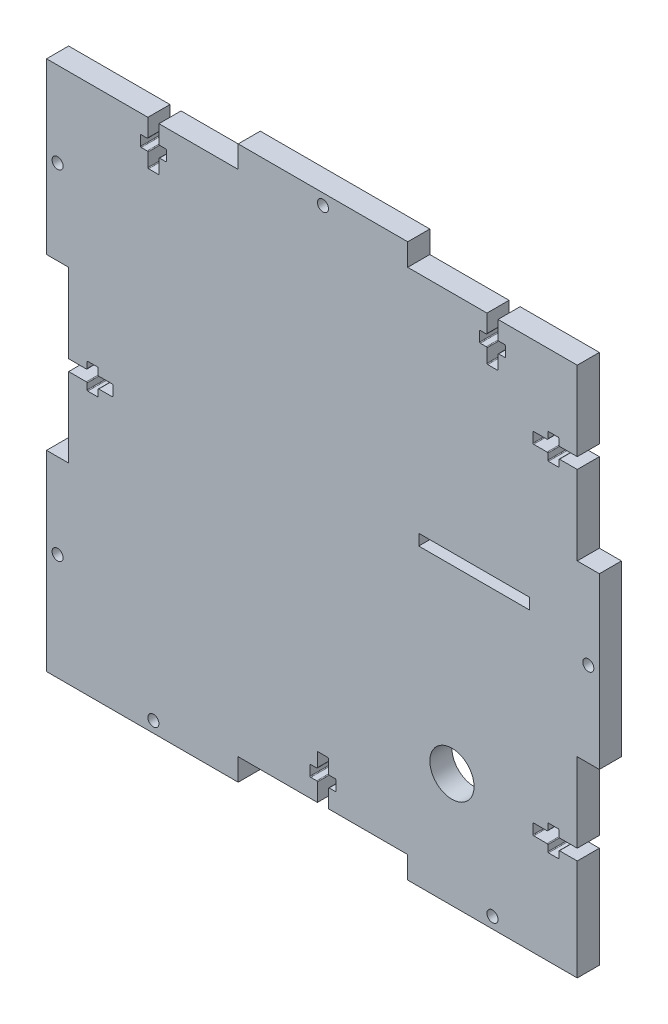
SolidWorks part; units mm, degrees
ref_plane "Front Plane" through (0, 0, 0) normal (0, 0, 1) x (1, 0, 0)
ref_plane "Top Plane" through (0, 0, 0) normal (0, 1, 0) x (1, 0, 0)
ref_plane "Right Plane" through (0, 0, 0) normal (1, 0, 0) x (0, 0, -1)
sketch "Sketch1" plane through (0, 0, 0) normal (0, 0, 1) x (1, 0, 0)
  line L0 (-69, 69) -> (-23, 69)
  line L5 (-75, -75) -> (75, -75) construction
  line L6 (-75, -75) -> (-75, 75) construction
  line L7 (-75, 75) -> (75, 75) construction
  line L8 (75, -75) -> (75, 75) construction
  line L9 (75, 23) -> (69, 23)
  line L10 (69, -23) -> (75, -23)
  line L11 (-69, -69) -> (69, -69) construction
  line L12 (-69, -69) -> (-69, 69) construction
  line L13 (-69, 69) -> (69, 69) construction
  line L14 (69, -69) -> (69, 69) construction
  line L15 (-69, -69) -> (69, 69) construction
  line L16 (69, -69) -> (69, -23)
  line L17 (-23, 69) -> (-23, 75)
  line L18 (-23, 75) -> (23, 75)
  line L19 (23, 75) -> (23, 69)
  line L20 (23, 69) -> (69, 69)
  line L21 (75, -23) -> (75, 23)
  line L22 (69, 23) -> (69, 69)
  line L23 (-75, 23) -> (-69, 23)
  line L24 (-69, 69) -> (-75, 69)
  line L25 (-75, 69) -> (-75, 23)
  line L26 (69, -69) -> (69, -75)
  line L27 (69, -75) -> (23, -75)
  line L28 (23, -75) -> (23, -69)
  line L29 (23, -69) -> (-23, -69)
  line L30 (-23, -69) -> (-23, -75)
  line L31 (-23, -75) -> (-69, -75)
  line L32 (-69, -75) -> (-69, -69) construction
  line L33 (-69, 23) -> (-69, -23)
  line L34 (-69, -23) -> (-75, -23)
  line L35 (-75, -23) -> (-75, -69)
  line L36 (-75, -69) -> (-69, -69) construction
  line L37 (-46, 69) -> (-46, -75) construction
  line L38 (-69, 69) -> (69, -69) construction
  line L39 (-75, -75) -> (-69, -75)
  line L40 (-75, -75) -> (-75, -69)
  point P0 (0, 0)
  point P6 (-7, -7)
  point P26 (0, -75)
  point P27 (-75, 0)
  dimension "D1" = 150
  dimension "D2" = 150
  dimension "D5" = 46
  dimension "D3" = 6
  dimension "D6" = 6
  dimension "D7" = 6
extrude "Box Side" add sketch "Sketch1" along normal blind 6
sketch "Sketch2" plane through (0, 0, 6) normal (0, 0, 1) x (1, 0, 0)
  line L0 (23, 72) -> (-23, 72) construction
  line L1 (23, 75) -> (23, 69) construction
  line L2 (-23, 69) -> (-23, 75) construction
  line L3 (-46, 69) -> (-46, -75) construction
  line L5 (0, 75) -> (0, 69) construction
  line L6 (-23, 75) -> (23, 75) construction
  line L7 (-69, 69) -> (69, 69) construction
  line L16 (-46, 69) -> (-46, -75) construction
  line L21 (0, -69) -> (0, 69) construction
  line L35 (-69, 69) -> (-23, 69) construction
  line L36 (-44.5, 69) -> (-44.5, 64.2)
  line L37 (-44.3, 64) -> (-42.7, 64)
  line L38 (-42.5, 63.8) -> (-42.5, 61.2)
  line L39 (-42.7, 61) -> (-44.3, 61)
  line L40 (-44.5, 60.8) -> (-44.5, 57.2)
  line L46 (-44.7, 57) -> (-47.3, 57)
  line L48 (-44.5, 69) -> (-47.5, 69)
  line L51 (-47.5, 60.8) -> (-47.5, 57.2)
  line L52 (-49.3, 61) -> (-47.7, 61)
  line L53 (-49.5, 63.8) -> (-49.5, 61.2)
  line L54 (-47.7, 64) -> (-49.3, 64)
  line L55 (-47.5, 69) -> (-47.5, 64.2)
  line L56 (47.5, 69) -> (47.5, 64.2)
  line L57 (47.7, 64) -> (49.3, 64)
  line L58 (49.5, 63.8) -> (49.5, 61.2)
  line L59 (49.3, 61) -> (47.7, 61)
  line L60 (47.5, 60.8) -> (47.5, 57.2)
  line L61 (44.5, 69) -> (47.5, 69)
  line L62 (44.7, 57) -> (47.3, 57)
  line L63 (44.5, 60.8) -> (44.5, 57.2)
  line L64 (42.7, 61) -> (44.3, 61)
  line L65 (42.5, 63.8) -> (42.5, 61.2)
  line L66 (44.3, 64) -> (42.7, 64)
  line L67 (44.5, 69) -> (44.5, 64.2)
  line L68 (-69, -69) -> (69, 69) construction
  line L69 (-69, -69) -> (69, 69) construction
  line L70 (75, 0) -> (69, 0) construction
  line L71 (72, 23) -> (72, -23) construction
  line L72 (69, 44.5) -> (64.2, 44.5)
  line L73 (64, 44.3) -> (64, 42.7)
  line L74 (63.8, 42.5) -> (61.2, 42.5)
  line L75 (61, 42.7) -> (61, 44.3)
  line L76 (60.8, 44.5) -> (57.2, 44.5)
  line L77 (57, 44.7) -> (57, 47.3)
  line L78 (69, 44.5) -> (69, 47.5)
  line L79 (60.8, 47.5) -> (57.2, 47.5)
  line L80 (61, 49.3) -> (61, 47.7)
  line L81 (63.8, 49.5) -> (61.2, 49.5)
  line L82 (64, 47.7) -> (64, 49.3)
  line L83 (69, 47.5) -> (64.2, 47.5)
  line L84 (69, -47.5) -> (64.2, -47.5)
  line L85 (64, -47.7) -> (64, -49.3)
  line L86 (63.8, -49.5) -> (61.2, -49.5)
  line L87 (61, -49.3) -> (61, -47.7)
  line L88 (60.8, -47.5) -> (57.2, -47.5)
  line L89 (69, -44.5) -> (69, -47.5)
  line L90 (57, -44.7) -> (57, -47.3)
  line L91 (60.8, -44.5) -> (57.2, -44.5)
  line L92 (61, -42.7) -> (61, -44.3)
  line L93 (63.8, -42.5) -> (61.2, -42.5)
  line L94 (64, -44.3) -> (64, -42.7)
  line L95 (69, -44.5) -> (64.2, -44.5)
  line L120 (-69, 69) -> (69, -69) construction
  line L121 (-69, 69) -> (69, -69) construction
  line L122 (-1.5, -69) -> (1.5, -69)
  line L123 (-23, -69) -> (23, -69) construction
  line L124 (1.5, -69) -> (1.5, -64.2)
  line L125 (1.7, -64) -> (3.3, -64)
  line L126 (3.5, -63.8) -> (3.5, -61.2)
  line L127 (3.3, -61) -> (1.7, -61)
  line L128 (1.5, -60.8) -> (1.5, -57.2)
  line L129 (1.3, -57) -> (-1.3, -57)
  line L130 (-1.5, -60.8) -> (-1.5, -57.2)
  line L131 (-3.3, -61) -> (-1.7, -61)
  line L132 (-3.5, -63.8) -> (-3.5, -61.2)
  line L133 (-1.7, -64) -> (-3.3, -64)
  line L134 (-1.5, -69) -> (-1.5, -64.2)
  line L135 (-69, -1.5) -> (-64.2, -1.5)
  line L136 (-64, -1.7) -> (-64, -3.3)
  line L137 (-63.8, -3.5) -> (-61.2, -3.5)
  line L138 (-61, -3.3) -> (-61, -1.7)
  line L139 (-60.8, -1.5) -> (-57.2, -1.5)
  line L140 (-57, 1.3) -> (-57, -1.3)
  line L141 (-60.8, 1.5) -> (-57.2, 1.5)
  line L142 (-61, 3.3) -> (-61, 1.7)
  line L143 (-63.8, 3.5) -> (-61.2, 3.5)
  line L144 (-64, 1.7) -> (-64, 3.3)
  line L145 (-69, 1.5) -> (-64.2, 1.5)
  line L146 (-69, -1.5) -> (-69, 1.5)
  line L147 (-69, -72) -> (-23, -72) construction
  line L148 (-23, 69) -> (-75, 69) construction
  line L149 (-23, -75) -> (-23, -69) construction
  line L150 (-69, -69) -> (-69, -75) construction
  line L151 (-75, -75) -> (-23, -75) construction
  circle A0 centre (0, 72) radius 1.5
  arc A1 (-44.5, 57.2) -> (-44.7, 57) centre (-44.7, 57.2) cw
  arc A2 (-44.3, 61) -> (-44.5, 60.8) centre (-44.3, 60.8) ccw
  arc A3 (-42.5, 61.2) -> (-42.7, 61) centre (-42.7, 61.2) cw
  arc A4 (-42.7, 64) -> (-42.5, 63.8) centre (-42.7, 63.8) cw
  arc A5 (-44.5, 64.2) -> (-44.3, 64) centre (-44.3, 64.2) ccw
  arc A6 (-47.5, 64.2) -> (-47.7, 64) centre (-47.7, 64.2) cw
  arc A7 (-49.3, 64) -> (-49.5, 63.8) centre (-49.3, 63.8) ccw
  arc A8 (-49.5, 61.2) -> (-49.3, 61) centre (-49.3, 61.2) ccw
  arc A9 (-47.7, 61) -> (-47.5, 60.8) centre (-47.7, 60.8) cw
  arc A10 (-47.5, 57.2) -> (-47.3, 57) centre (-47.3, 57.2) ccw
  arc A11 (47.5, 57.2) -> (47.3, 57) centre (47.3, 57.2) cw
  arc A12 (47.7, 61) -> (47.5, 60.8) centre (47.7, 60.8) ccw
  arc A13 (49.5, 61.2) -> (49.3, 61) centre (49.3, 61.2) cw
  arc A14 (49.3, 64) -> (49.5, 63.8) centre (49.3, 63.8) cw
  arc A15 (47.5, 64.2) -> (47.7, 64) centre (47.7, 64.2) ccw
  arc A16 (44.5, 64.2) -> (44.3, 64) centre (44.3, 64.2) cw
  arc A17 (42.7, 64) -> (42.5, 63.8) centre (42.7, 63.8) ccw
  arc A18 (42.5, 61.2) -> (42.7, 61) centre (42.7, 61.2) ccw
  arc A19 (44.3, 61) -> (44.5, 60.8) centre (44.3, 60.8) cw
  arc A20 (44.5, 57.2) -> (44.7, 57) centre (44.7, 57.2) ccw
  arc A21 (57.2, 44.5) -> (57, 44.7) centre (57.2, 44.7) cw
  arc A22 (61, 44.3) -> (60.8, 44.5) centre (60.8, 44.3) ccw
  arc A23 (61.2, 42.5) -> (61, 42.7) centre (61.2, 42.7) cw
  arc A24 (64, 42.7) -> (63.8, 42.5) centre (63.8, 42.7) cw
  arc A25 (64.2, 44.5) -> (64, 44.3) centre (64.2, 44.3) ccw
  arc A26 (64.2, 47.5) -> (64, 47.7) centre (64.2, 47.7) cw
  arc A27 (64, 49.3) -> (63.8, 49.5) centre (63.8, 49.3) ccw
  arc A28 (61.2, 49.5) -> (61, 49.3) centre (61.2, 49.3) ccw
  arc A29 (61, 47.7) -> (60.8, 47.5) centre (60.8, 47.7) cw
  arc A30 (57.2, 47.5) -> (57, 47.3) centre (57.2, 47.3) ccw
  arc A31 (57.2, -47.5) -> (57, -47.3) centre (57.2, -47.3) cw
  arc A32 (61, -47.7) -> (60.8, -47.5) centre (60.8, -47.7) ccw
  arc A33 (61.2, -49.5) -> (61, -49.3) centre (61.2, -49.3) cw
  arc A34 (64, -49.3) -> (63.8, -49.5) centre (63.8, -49.3) cw
  arc A35 (64.2, -47.5) -> (64, -47.7) centre (64.2, -47.7) ccw
  arc A36 (64.2, -44.5) -> (64, -44.3) centre (64.2, -44.3) cw
  arc A37 (64, -42.7) -> (63.8, -42.5) centre (63.8, -42.7) ccw
  arc A38 (61.2, -42.5) -> (61, -42.7) centre (61.2, -42.7) ccw
  arc A39 (61, -44.3) -> (60.8, -44.5) centre (60.8, -44.3) cw
  arc A40 (57.2, -44.5) -> (57, -44.7) centre (57.2, -44.7) ccw
  circle A41 centre (72, 0) radius 1.5
  arc A62 (1.5, -57.2) -> (1.3, -57) centre (1.3, -57.2) ccw
  arc A63 (1.7, -61) -> (1.5, -60.8) centre (1.7, -60.8) cw
  arc A64 (3.5, -61.2) -> (3.3, -61) centre (3.3, -61.2) ccw
  arc A65 (3.3, -64) -> (3.5, -63.8) centre (3.3, -63.8) ccw
  arc A66 (1.5, -64.2) -> (1.7, -64) centre (1.7, -64.2) cw
  arc A67 (-1.5, -64.2) -> (-1.7, -64) centre (-1.7, -64.2) ccw
  arc A68 (-3.3, -64) -> (-3.5, -63.8) centre (-3.3, -63.8) cw
  arc A69 (-3.5, -61.2) -> (-3.3, -61) centre (-3.3, -61.2) cw
  arc A70 (-1.7, -61) -> (-1.5, -60.8) centre (-1.7, -60.8) ccw
  arc A71 (-1.5, -57.2) -> (-1.3, -57) centre (-1.3, -57.2) cw
  arc A72 (-57.2, -1.5) -> (-57, -1.3) centre (-57.2, -1.3) ccw
  arc A73 (-61, -1.7) -> (-60.8, -1.5) centre (-60.8, -1.7) cw
  arc A74 (-61.2, -3.5) -> (-61, -3.3) centre (-61.2, -3.3) ccw
  arc A75 (-64, -3.3) -> (-63.8, -3.5) centre (-63.8, -3.3) ccw
  arc A76 (-64.2, -1.5) -> (-64, -1.7) centre (-64.2, -1.7) cw
  arc A77 (-64.2, 1.5) -> (-64, 1.7) centre (-64.2, 1.7) ccw
  arc A78 (-64, 3.3) -> (-63.8, 3.5) centre (-63.8, 3.3) cw
  arc A79 (-61.2, 3.5) -> (-61, 3.3) centre (-61.2, 3.3) cw
  arc A80 (-61, 1.7) -> (-60.8, 1.5) centre (-60.8, 1.7) ccw
  arc A81 (-57.2, 1.5) -> (-57, 1.3) centre (-57.2, 1.3) cw
  circle A82 centre (-46, -72) radius 1.5
  circle A83 centre (46, -72) radius 1.5
  circle A84 centre (-72, 46) radius 1.5
  circle A85 centre (-72, -46) radius 1.5
  point P6 (0, 72)
  point P38 (0, 0)
  point P56 (-46, 57)
  point P88 (46, 57)
  point P161 (57, 46)
  point P162 (57, -46)
  point P198 (0, -57)
  point P231 (-57, 0)
  point P234 (-42.5, 62.5)
  dimension "D1" = 3
  dimension "D2" = 0.2
  dimension "D8" = 0.2
  dimension "D14" = 3
  dimension "D4" = 3
  dimension "D7" = 1.5
  dimension "D10" = 3
  dimension "D12" = 1.5
  dimension "D9" = 12
  dimension "D11" = 5
  dimension "D13" = 7
  dimension "D3" = 12
  dimension "D5" = 7
  dimension "D6" = 5
extrude "Screw Cut-outs" cut sketch "Sketch2" against normal through all
sketch "Bearing Hole" plane through (0, 0, 6) normal (0, 0, 1) x (1, 0, 0)
  line L0 (17, -69) -> (50017, -69) construction
  line L4 (35, -41) -> (50035, -41) construction
  line L5 (35.5774, -47) -> (50035.5774, -47) construction
  line L8 (38, -52) -> (38, -50052) construction
  line L9 (69, -75) -> (69, -47.5) construction
  circle A0 centre (35, -44) radius 3 construction
  circle A1 centre (35, -54) radius 15 construction
  circle A2 centre (35, -44) radius 6
  point P16 (0, 0)
  dimension "D2" = 6
  dimension "D4" = 30
  dimension "D5" = 12
  dimension "D1" = 7
  dimension "D3" = 31
extrude "Shaft Hole" cut sketch "Bearing Hole" against normal through all
sketch "Sketch4" plane through (0, 0, 0) normal (0, 0, -1) x (-1, 0, 0)
  line L0 (-72, 1.5) -> (49928, 1.5) construction
  line L1 (-56, 8) -> (-26, 8)
  line L2 (-56, 8) -> (-56, 5)
  line L3 (-56, 5) -> (-26, 5)
  line L4 (-26, 8) -> (-26, 5)
  line L5 (-75, -23) -> (-75, 23) construction
  circle A1 centre (-72, 0) radius 1.5 construction
  dimension "D1" = 3.5
  dimension "D2" = 30
  dimension "D3" = 3
  dimension "D4" = 19
extrude "Grooves" cut sketch "Sketch4" against normal up to surface (6 mm away) up to face at (41, -44, 6)
equation "\"filletRadius\"=0.2"
equation "\"D8@Sketch2\"=\"filletRadius\""
equation "\"D2@Sketch2\"=\"filletRadius\""
equation "\"fingerWidth\"= 46"
equation "\"D5@Sketch1\"=\"fingerWidth\""
equation "\"wallThickness\"= 6"
equation "\"D3@Sketch1\" = \"wallThickness\""
equation "\"D6@Sketch1\" = \"wallThickness\""
equation "\"D7@Sketch1\" = \"wallThickness\""
equation "\"D1@Box Side\" = \"wallThickness\""
equation "\"M3\"= 3"
equation "\"D14@Sketch2\"=\"M3\""
equation "\"D1@Sketch2\"=\"M3\""
equation "\"D12@Sketch2\"=\"M3\"/2"
equation "\"nutThickness\"=3"
equation "\"D10@Sketch2\" = \"nutThickness\""
equation "\"boltLength\"= 12"
equation "\"D9@Sketch2\" = \"boltLength\""
equation "\"distanceToNut\"= 5"
equation "\"D11@Sketch2\" = \"distanceToNut\""
equation "\"D13@Sketch2\" = \"nutWidth\""
equation "\"D7@Sketch2\"=\"M3\"/2"
equation "\"D4@Sketch2\" = \"nutThickness\""
equation "\"D3@Sketch2\" = \"boltLength\""
equation "\"D5@Sketch2\" = \"nutWidth\""
equation "\"D6@Sketch2\" = \"distanceToNut\""
equation "\"sideLength\"=150"
equation "\"D1@Sketch1\"=\"sideLength\""
equation "\"D2@Sketch1\"=\"sideLength\""
equation "\"nutWidth\"=7"
